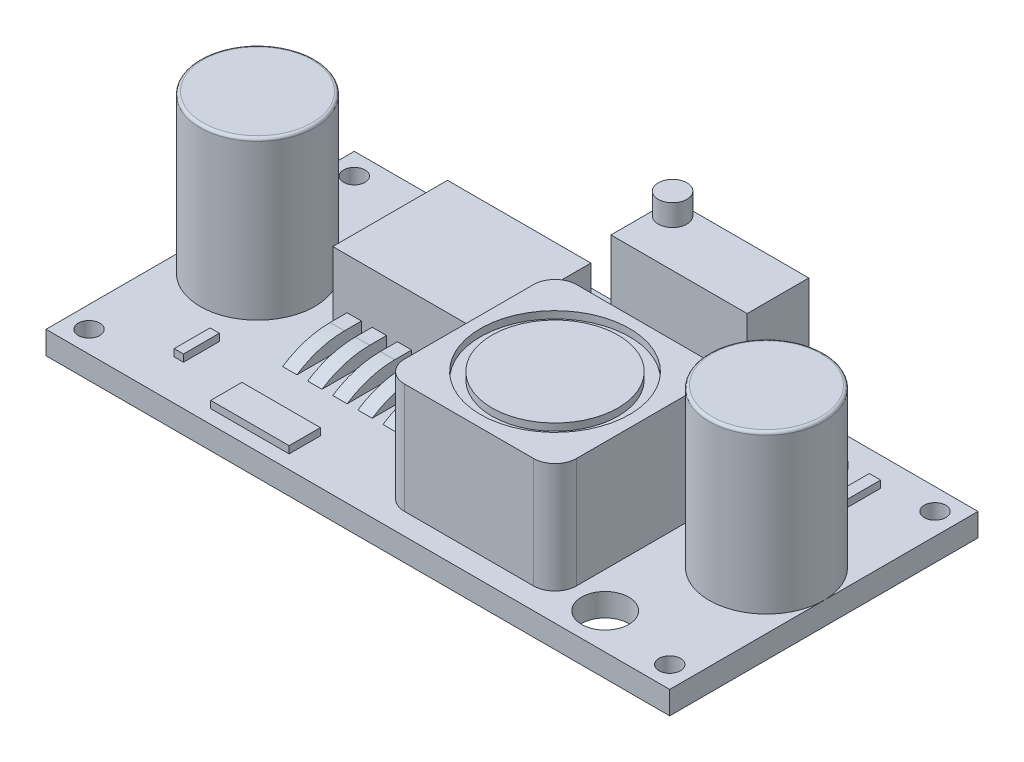
SolidWorks part; units mm, degrees
ref_plane "Alzado" through (0, 0, 0) normal (0, 0, 1) x (1, 0, 0)
ref_plane "Planta" through (0, 0, 0) normal (0, 1, 0) x (1, 0, 0)
ref_plane "Vista lateral" through (0, 0, 0) normal (1, 0, 0) x (0, 0, -1)
sketch "Croquis1" plane through (0, 0, 0) normal (0, 1, 0) x (1, 0, 0)
  line L1 (-21.75, 10.75) -> (21.75, 10.75)
  line L2 (-21.75, 10.75) -> (-21.75, -10.75)
  line L3 (-21.75, -10.75) -> (21.75, -10.75)
  line L4 (21.75, 10.75) -> (21.75, -10.75)
  line L5 (-21.75, 10.75) -> (21.75, -10.75) construction
  line L6 (-21.75, -10.75) -> (21.75, 10.75) construction
  point P0 (0, 0)
  dimension "D1" = 21.5
  dimension "D2" = 43.5
extrude "Saliente-Extruir1" add sketch "Croquis1" against normal blind 1.6
sketch "Croquis2" plane through (0, 0, 0) normal (0, 1, 0) x (1, 0, 0)
  line L0 (21.75, -10.75) -> (21.75, 10.75) construction
  line L1 (-21.75, -10.75) -> (21.75, -10.75) construction
  line L2 (0, 10.75) -> (0, -10.75) construction
  line L3 (21.75, 0) -> (-21.75, 0) construction
  line L4 (-21.75, 10.75) -> (-21.75, -10.75) construction
  circle A0 centre (14.75, -8.25) radius 1.65
  circle A1 centre (-14.75, -8.25) radius 1.65 construction
  circle A2 centre (-14.75, 8.25) radius 1.65
  circle A3 centre (20.25, -9.25) radius 0.75
  circle A4 centre (-20.25, -9.25) radius 0.75
  circle A5 centre (20.25, 9.25) radius 0.75
  circle A6 centre (-20.25, 9.25) radius 0.75
  point P10 (0, 0)
  point P16 (0, 0)
  dimension "D1" = 3.3
  dimension "D4" = 1.5
  dimension "D2" = 7
  dimension "D3" = 2.5
  dimension "D5" = 1.5
  dimension "D6" = 1.5
extrude "Cortar-Extruir1" cut sketch "Croquis2" against normal up to next
sketch "Croquis3" plane through (0, 0, 0) normal (0, 1, 0) x (1, 0, 0)
  line L0 (21.75, -10.75) -> (21.75, 10.75) construction
  line L1 (0, 0) -> (0, 10.75) construction
  line L2 (21.75, 10.75) -> (-21.75, 10.75) construction
  circle A0 centre (17.75, 0) radius 4
  circle A1 centre (-17.75, 0) radius 4
  dimension "D1" = 8
extrude "Saliente-Extruir2" add sketch "Croquis3" along normal blind 11 separate body
fillet "Redondeo1" radius 0.2 1 edges at (-17.75, 11, -4)
fillet "Redondeo2" radius 0.2 1 edges at (17.75, 11, 4)
sketch "Croquis4" plane through (0, 0, 0) normal (0, 1, 0) x (1, 0, 0)
  line L0 (-21.75, -10.75) -> (21.75, -10.75) construction
  line L1 (1.75, 2.75) -> (10.75, 2.75)
  line L2 (0.25, 1.25) -> (0.25, -7.75)
  line L3 (1.75, -9.25) -> (10.75, -9.25)
  line L4 (12.25, 1.25) -> (12.25, -7.75)
  circle A0 centre (17.75, 0) radius 4 construction
  arc A1 (10.75, -9.25) -> (12.25, -7.75) centre (10.75, -7.75) ccw
  arc A2 (0.25, -7.75) -> (1.75, -9.25) centre (1.75, -7.75) ccw
  arc A3 (10.75, 2.75) -> (12.25, 1.25) centre (10.75, 1.25) cw
  arc A4 (1.75, 2.75) -> (0.25, 1.25) centre (1.75, 1.25) ccw
  point P14 (12.25, 2.75)
  point P17 (0.25, 2.75)
  dimension "D3" = 5.5
  dimension "D4" = 1.5
  dimension "D1" = 12
  dimension "D2" = 1.5
extrude "Saliente-Extruir3" add sketch "Croquis4" along normal blind 7.7 separate body
sketch "Croquis5" plane through (0, 7.7, 0) normal (0, 1, 0) x (1, 0, 0)
  line L0 (10.75, 2.75) -> (1.75, 2.75) construction
  line L1 (0.25, 1.25) -> (0.25, -7.75) construction
  circle A0 centre (6.25, -3.25) radius 4.4
  circle A1 centre (6.25, -3.25) radius 5.2
  point P4 (6.25, 2.75)
  point P7 (0.25, -3.25)
  dimension "D1" = 8.8
  dimension "D2" = 0.8
extrude "Cortar-Extruir2" cut sketch "Croquis5" against normal blind 0.5
sketch "Croquis6" plane through (0, 0, 0) normal (0, 1, 0) x (1, 0, 0)
  line L0 (21.75, 10.75) -> (-21.75, 10.75) construction
  line L1 (2.25, 8.95) -> (11.75, 8.95)
  line L2 (2.25, 8.95) -> (2.25, 4.65)
  line L3 (2.25, 4.65) -> (11.75, 4.65)
  line L4 (11.75, 8.95) -> (11.75, 4.65)
  line L5 (21.75, -10.75) -> (21.75, 10.75) construction
  dimension "D1" = 9.5
  dimension "D2" = 4.3
  dimension "D3" = 1.8
  dimension "D4" = 10
extrude "Saliente-Extruir4" add sketch "Croquis6" along normal blind 10 separate body
sketch "Croquis7" plane through (0, 10, 0) normal (0, 1, 0) x (1, 0, 0)
  line L0 (11.75, 8.95) -> (2.25, 8.95) construction
  line L1 (2.25, 8.95) -> (2.25, 4.65) construction
  circle A0 centre (3.25, 7.95) radius 1
  dimension "D1" = 2
extrude "Saliente-Extruir5" add sketch "Croquis7" along normal blind 1.5 separate body
sketch "Croquis8" plane through (0, 0, 0) normal (0, 1, 0) x (1, 0, 0)
  line L0 (21.75, 10.75) -> (-21.75, 10.75) construction
  line L1 (-12.25, 7.75) -> (-2.25, 7.75)
  line L2 (-12.25, 7.75) -> (-12.25, -0.25)
  line L3 (-12.25, -0.25) -> (-2.25, -0.25)
  line L4 (-2.25, 7.75) -> (-2.25, -0.25)
  line L5 (-21.75, 10.75) -> (-21.75, -10.75) construction
  dimension "D1" = 10
  dimension "D2" = 8
  dimension "D3" = 3
  dimension "D4" = 9.5
extrude "Saliente-Extruir6" add sketch "Croquis8" along normal blind 4.5 separate body
sketch "Croquis9" plane through (0, 0, 0) normal (0, 1, 0) x (1, 0, 0)
  line L0 (-12.25, -0.25) -> (-2.25, -0.25) construction
  line L1 (-11.25, -0.25) -> (-10.25, -0.25)
  line L2 (-11.25, -0.25) -> (-11.25, -4.75)
  line L3 (-11.25, -4.75) -> (-10.25, -4.75)
  line L4 (-10.25, -0.25) -> (-10.25, -4.75)
  line L5 (-12.25, 7.75) -> (-12.25, -0.25) construction
  line L6 (-9.5, -0.25) -> (-9.5, -4.75)
  line L7 (-9.5, -0.25) -> (-8.5, -0.25)
  line L8 (-8.5, -0.25) -> (-8.5, -4.75)
  line L9 (-9.5, -4.75) -> (-8.5, -4.75)
  line L10 (-7.75, -0.25) -> (-7.75, -4.75)
  line L11 (-7.75, -0.25) -> (-6.75, -0.25)
  line L12 (-6.75, -0.25) -> (-6.75, -4.75)
  line L13 (-7.75, -4.75) -> (-6.75, -4.75)
  line L14 (-6, -0.25) -> (-6, -4.75)
  line L15 (-6, -0.25) -> (-5, -0.25)
  line L16 (-5, -0.25) -> (-5, -4.75)
  line L17 (-6, -4.75) -> (-5, -4.75)
  line L18 (-4.25, -0.25) -> (-4.25, -4.75)
  line L19 (-4.25, -0.25) -> (-3.25, -0.25)
  line L20 (-3.25, -0.25) -> (-3.25, -4.75)
  line L21 (-4.25, -4.75) -> (-3.25, -4.75)
  line L22 (-2.25, -0.25) -> (-2.25, 7.75) construction
  dimension "D1" = 1
  dimension "D2" = 1
  dimension "D3" = 4.5
  dimension "D5" = 1
  dimension "D4" = 5
extrude "Saliente-Extruir7" add sketch "Croquis9" along normal blind 1 separate body
fillet "Redondeo4" radius 6 1 edges at (-10.75, 1, 4.75)
fillet "Redondeo5" radius 6 1 edges at (-9, 1, 4.75)
fillet "Redondeo6" radius 6 1 edges at (-7.25, 1, 4.75)
fillet "Redondeo7" radius 6 1 edges at (-5.5, 1, 4.75)
fillet "Redondeo8" radius 6 1 edges at (-3.75, 1, 4.75)
sketch "Croquis10" plane through (0, 0, 0) normal (0, 1, 0) x (1, 0, 0)
  line L0 (-2.25, 7.75) -> (-12.25, 7.75) construction
  line L1 (-12.25, 7.75) -> (-2.25, 7.75)
  line L2 (-12.25, 7.75) -> (-12.25, 9.75)
  line L3 (-12.25, 9.75) -> (-2.25, 9.75)
  line L4 (-2.25, 7.75) -> (-2.25, 9.75)
  line L5 (21.75, 10.75) -> (-21.75, 10.75) construction
  dimension "D1" = 1
extrude "Saliente-Extruir8" add sketch "Croquis10" along normal blind 1 separate body
sketch "Croquis11" plane through (0, 0, 0) normal (0, 1, 0) x (1, 0, 0)
  line L1 (-11.2133, -7.6222) -> (-5.7456, -7.6222)
  line L2 (-11.2133, -7.6222) -> (-11.2133, -9.8)
  line L3 (-11.2133, -9.8) -> (-5.7456, -9.8)
  line L4 (-5.7456, -7.6222) -> (-5.7456, -9.8)
  line L5 (-14.9665, -7.9466) -> (-15.6152, -7.9466)
  line L6 (-14.9665, -7.9466) -> (-14.9665, -5.4445)
  line L7 (-14.9665, -5.4445) -> (-15.6152, -5.4445)
  line L8 (-15.6152, -7.9466) -> (-15.6152, -5.4445)
  line L9 (-0.6487, 8.75) -> (0, 8.75)
  line L10 (-0.6487, 8.75) -> (-0.6487, 6.0932)
  line L11 (-0.6487, 6.0932) -> (0, 6.0932)
  line L12 (0, 8.75) -> (0, 6.0932)
  line L13 (-0.6487, 5.0274) -> (0, 5.0274)
  line L14 (-0.6487, 5.0274) -> (-0.6487, 2.8033)
  line L15 (-0.6487, 2.8033) -> (0, 2.8033)
  line L16 (0, 5.0274) -> (0, 2.8033)
  line L17 (13.7617, 8.75) -> (14.6885, 8.75)
  line L18 (13.7617, 8.75) -> (13.7617, 5.0274)
  line L19 (13.7617, 5.0274) -> (14.6885, 5.0274)
  line L20 (14.6885, 8.75) -> (14.6885, 5.0274)
  line L21 (16.1712, 8.75) -> (16.9589, 8.75)
  line L22 (16.1712, 8.75) -> (16.1712, 5.0274)
  line L23 (16.1712, 5.0274) -> (16.9589, 5.0274)
  line L24 (16.9589, 8.75) -> (16.9589, 5.0274)
extrude "Saliente-Extruir9" add sketch "Croquis11" along normal blind 0.5 separate body
